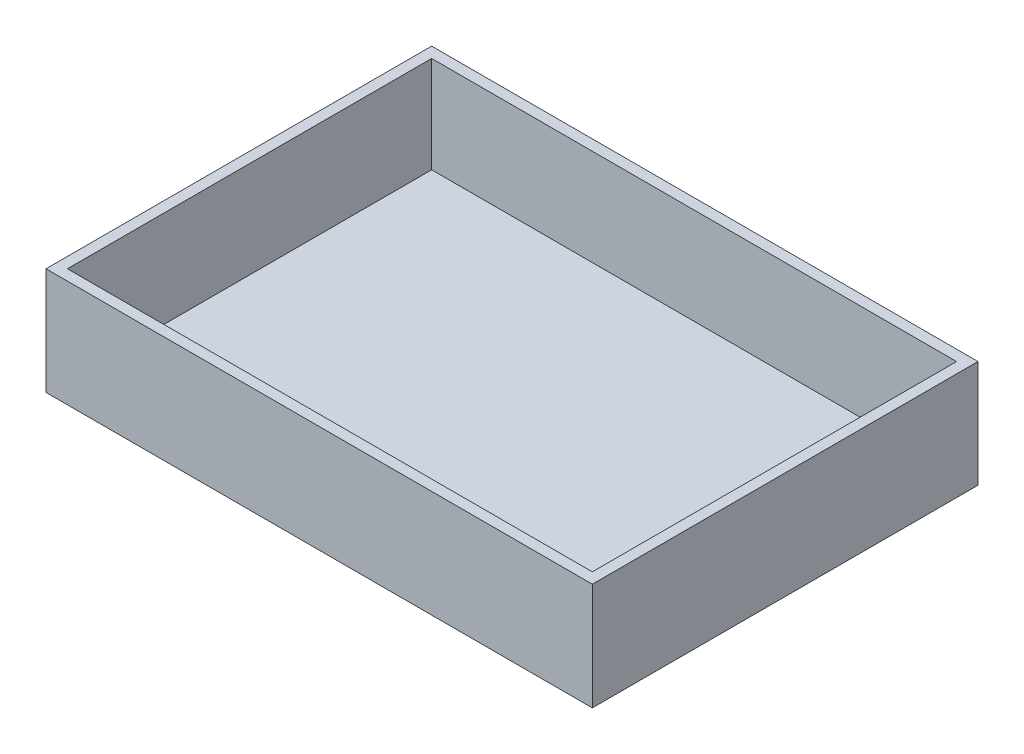
SolidWorks part; units mm, degrees
ref_plane "Front Plane" through (0, 0, 0) normal (0, 0, 1) x (1, 0, 0)
ref_plane "Top Plane" through (0, 0, 0) normal (0, 1, 0) x (1, 0, 0)
ref_plane "Right Plane" through (0, 0, 0) normal (1, 0, 0) x (0, 0, -1)
sketch "Sketch1" plane through (0, 0, 0) normal (0, 1, 0) x (1, 0, 0)
  line L1 (0, 0) -> (-153, 0)
  line L2 (0, 0) -> (0, -108)
  line L3 (0, -108) -> (-153, -108)
  line L4 (-153, 0) -> (-153, -108)
extrude "Boss-Extrude1" add sketch "Sketch1" along normal blind 30 contours L1 L4 L3 L2
shell "Shell1" thickness 3 removed face at (-76.5, 30, 54)
sketch "Sketch2" plane through (0, 30, 0) normal (0, 1, 0) x (1, 0, 0)
  line L0 (-156.646, -0.9017) -> (-153, -0.9017)
  line L2 (-153, 0) -> (-153, -108) construction
  line L3 (-153, -0.9017) -> (-153, -7.0118)
  line L4 (-153, -7.0118) -> (-156.646, -7.0118)
  circle A0 centre (-156.646, -3.9568) radius 1.769
  arc A1 (-156.646, -0.9017) -> (-156.646, -7.0118) centre (-156.646, -3.9568) ccw
